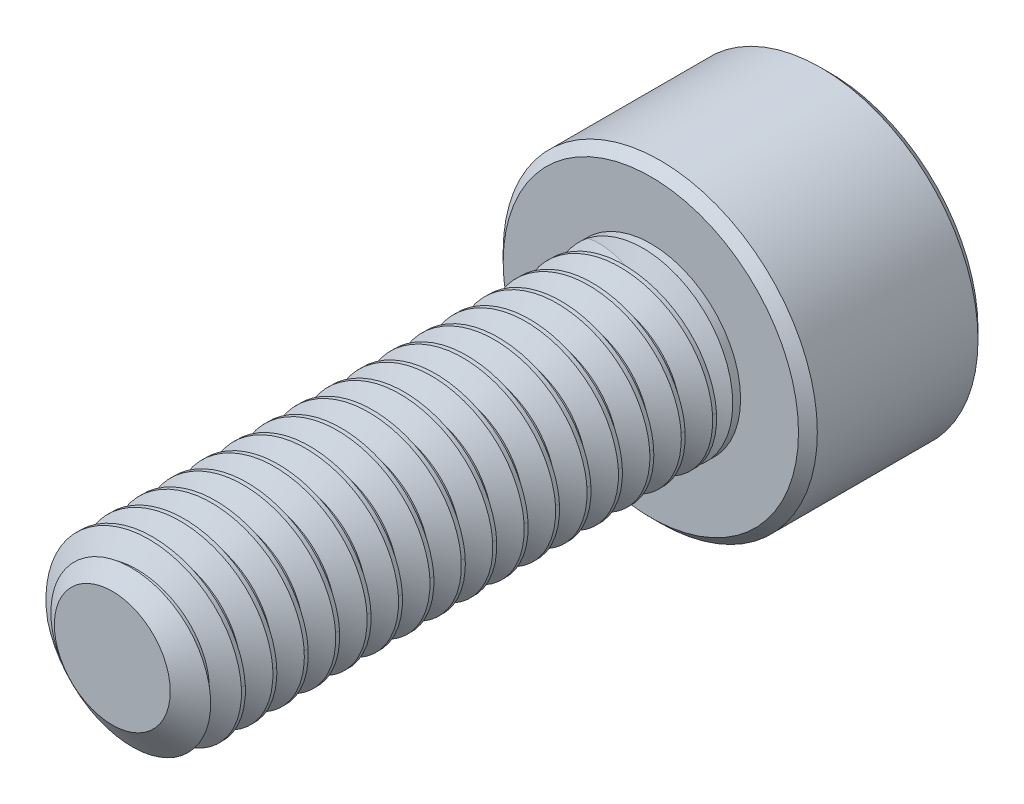
SolidWorks part; units mm, degrees
material "Alloy Steel"
ref_plane "Front Plane" through (0, 0, 0) normal (0, 0, 1) x (1, 0, 0)
ref_plane "Top Plane" through (0, 0, 0) normal (0, 1, 0) x (1, 0, 0)
ref_plane "Right Plane" through (0, 0, 0) normal (1, 0, 0) x (0, 0, -1)
sketch "Sketch1" plane through (0, 0, 0) normal (0, 0, 1) x (1, 0, 0)
  circle A0 centre (0, 0) radius 2
  dimension "OD" = 4
extrude "Extrude1" add sketch "Sketch1" against normal blind 12
sketch "Sketch2" plane through (0, 0, 0) normal (0, 0, 1) x (1, 0, 0)
  circle A0 centre (0, 0) radius 2 construction
  circle A1 centre (0, 0) radius 2
curve "Helix/Spiral1" pitch 0.7 height 12.7 radius 2 centre (0, 0, 0) axis (0, 0, -1) start towards (0, 1, 0) parameters "pitch"=0.7
sketch "Sketch3" plane through (0, 0, 0) normal (1, 0, 0) x (0, 0, -1)
  line L0 (-0.6125, 2) -> (-0.35, 1.5453)
  line L1 (-0.35, 1.5453) -> (-0.2625, 1.5453)
  line L2 (-0.2625, 1.5453) -> (0, 2)
  line L3 (-0.6125, 2) -> (0, 2)
  line L4 (-0.3062, 2) -> (-0.3063, 1.5453) construction
  line L5 (-0.4813, 1.7727) -> (-0.1313, 1.7727) construction
  line L6 (0, 2) -> (0, -2) construction
  line L7 (0, -2) -> (12, -2) construction
  point P11 (3.15, -2)
  dimension "D1" = 0.0875
  dimension "D2" = 0.35
  dimension "D3" = 60
  dimension "D4" = 3.15
sweep "Cut-Sweep1" cut profiles "Sketch3" path "Helix/Spiral1" align with end faces yes
sketch "Sketch4" plane through (0, 0, 0) normal (1, 0, 0) x (0, 0, -1)
  line L0 (0.4962, 2) -> (0, 1.2913)
  line L1 (0, 1.2913) -> (0, 2)
  line L2 (0.4962, 2) -> (0, 2)
  line L3 (-0.6125, 2) -> (0, 2) construction
  line L4 (0, 0) -> (7.0209, 0) construction
  dimension "D1" = 55
  dimension "D2" = 0.254
revolve "Cut-Revolve1" cut sketch "Sketch4" angle 360 about L4
sketch "Sketch5" plane through (0, 0, 0) normal (1, 0, 0) x (0, 0, -1)
  line L0 (12, -0.9741) -> (12, 1.9864) construction
  line L1 (12, 2) -> (0.1202, 2)
  line L2 (12, 2) -> (12, 0)
  line L3 (12, 0) -> (0, 0)
  line L4 (0, 1.6698) -> (0, 0)
  line L5 (0.1202, 2) -> (0, 1.6698)
  line L6 (0, 0) -> (9.9695, 0) construction
  point P3 (0, 2)
  point P10 (0, 2)
  dimension "D1" = 0.3302
  dimension "D3" = 20
  dimension "Thread Min" = 0
revolve "partially thread" [suppressed] add sketch "Sketch5" angle 360 about L6
sketch "Sketch6" plane through (0, 0, -12) normal (0, 0, -1) x (-1, 0, 0)
  circle A0 centre (0, 0) radius 3.5
  dimension "head dia" = 7
extrude "Extrude2" add sketch "Sketch6" along normal blind 4
sketch "Sketch7" plane through (0, 0, -16) normal (0, 0, -1) x (-1, 0, 0)
  line L1 (0, 1.7321) -> (-1.5, 0.866)
  line L2 (-1.5, 0.866) -> (-1.5, -0.866)
  line L3 (-1.5, -0.866) -> (0, -1.7321)
  line L4 (0, -1.7321) -> (1.5, -0.866)
  line L5 (1.5, -0.866) -> (1.5, 0.866)
  line L6 (1.5, 0.866) -> (0, 1.7321)
  circle A0 centre (0, 0) radius 1.5 construction
  dimension "hex dia" = 3
extrude "Cut-Extrude1" cut sketch "Sketch7" against normal blind 2.25
sketch "Sketch8" plane through (0, 0, -16) normal (0, 0, -1) x (-1, 0, 0)
  circle A0 centre (0, 0) radius 1.7321
extrude "Cut-Extrude2" cut sketch "Sketch8" against normal through all draft 45
chamfer "Chamfer1" distance 0.21 angle 45 2 edges at (-3.5, 0, -16) (-3.5, 0, -12)
sketch "Sketch9" plane through (0, 0, 0) normal (1, 0, 0) x (0, 0, -1)
  line L0 (0, 2) -> (0, -2) construction
  line L1 (3.85, 2) -> (3.85, -2) construction
  dimension "D1" = 3.85
sketch "Sketch10" plane through (0, 0, 0) normal (1, 0, 0) x (0, 0, -1)
  line L0 (12, 2) -> (12, 0)
  line L1 (12, 2) -> (11.825, 2)
  line L2 (11.825, 2) -> (10.9966, 0)
  line L3 (12, 0) -> (10.9966, 0)
  line L4 (12, 3.29) -> (12, -3.29) construction
  dimension "D1" = 22.5
  dimension "D2" = 0.175
revolve "Revolve1" add sketch "Sketch10" angle 360 about L3
equation "\"D3@Helix/Spiral1\" = \"screw length@Extrude1\"+\"pitch@Helix/Spiral1\""
equation "\"D1@Sketch3\" = \"pitch@Helix/Spiral1\"*.125"
equation "\"D2@Sketch3\" = \"pitch@Helix/Spiral1\"*.5"
equation "\"D1@Cut-Extrude1\" = \"hex dia@Sketch7\"*.75"
equation "\"D1@Chamfer1\" = \"head dia@Sketch6\"*.03"
equation "\"D1@Sketch9\" = \"pitch@Helix/Spiral1\"*5.5"
equation "\"D2@Sketch10\" = \"pitch@Helix/Spiral1\"*.25"
equation "\"D4@Sketch3\" = \"pitch@Helix/Spiral1\"*4.50"
